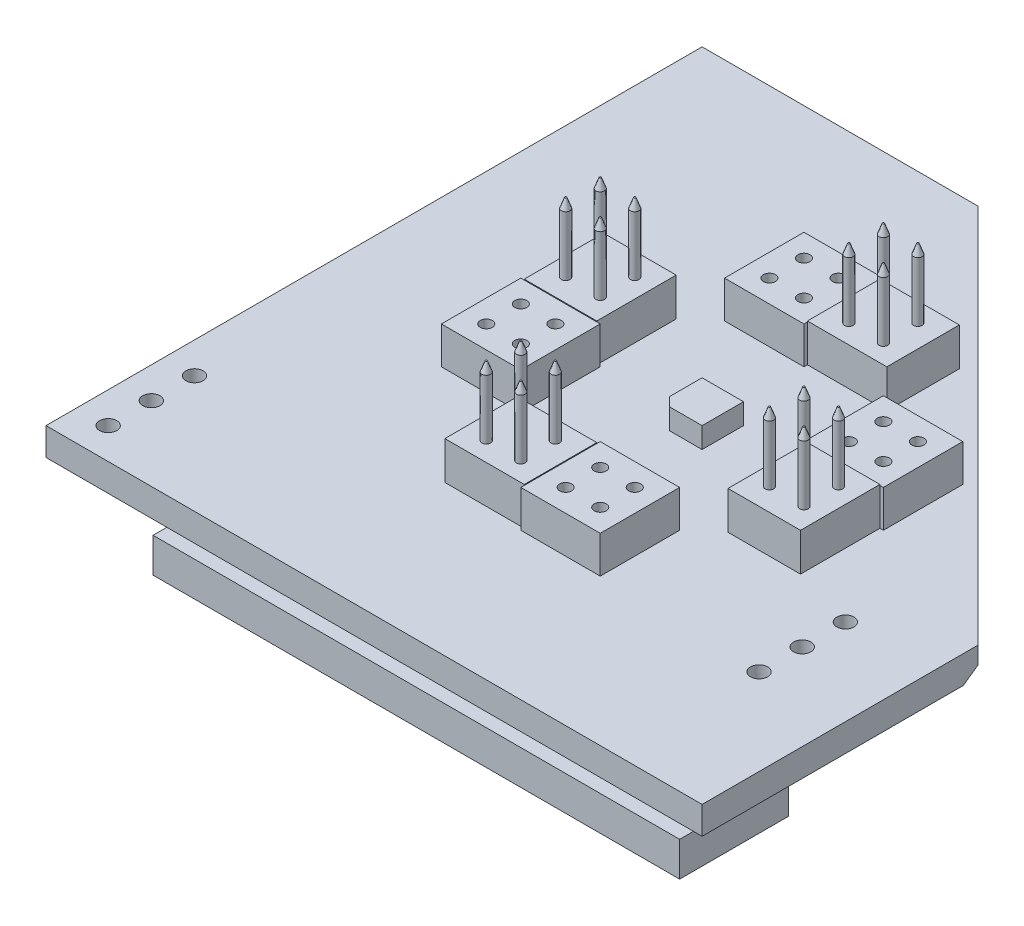
SolidWorks part; units mm, degrees
ref_plane "Front" through (0, 0, 0) normal (0, 0, 1) x (1, 0, 0)
ref_plane "Top" through (0, 0, 0) normal (0, 1, 0) x (1, 0, 0)
ref_plane "Right" through (0, 0, 0) normal (1, 0, 0) x (0, 0, -1)
sketch "Sketch1" plane through (0, 0, 0) normal (0, 1, 0) x (1, 0, 0)
  line L0 (19, -3.0194) -> (-3.0194, 19)
  line L1 (-19, 19) -> (-3.0194, 19)
  line L2 (-19, 19) -> (-19, -19)
  line L3 (-19, -19) -> (19, -19)
  line L4 (19, -3.0194) -> (19, -19)
  dimension "D1" = 19
  dimension "D2" = 19
  dimension "D3" = 19
  dimension "D4" = 19
  dimension "D5" = 45
  dimension "D6" = 11.3
extrude "Extrude1" add sketch "Sketch1" along normal blind 1.6
sketch "Sketch2" plane through (0, 1.6, 0) normal (0, 1, 0) x (-1, 0, 0)
  line L0 (-10.5, -4.6) -> (-10.5, 0)
  line L1 (4.6, -10.5) -> (0, -10.5)
  line L2 (4.6, -10.5) -> (4.6, -5.9)
  line L3 (4.6, -5.9) -> (0, -5.9)
  line L4 (0, -10.5) -> (0, -5.9)
  line L5 (-10.5, -4.6) -> (-5.9, -4.6)
  line L6 (-5.9, -4.6) -> (-5.9, 0)
  line L7 (-10.5, 0) -> (-5.9, 0)
  line L8 (-4.6, 10.5) -> (0, 10.5)
  line L9 (-4.6, 10.5) -> (-4.6, 5.9)
  line L10 (-4.6, 5.9) -> (0, 5.9)
  line L11 (0, 10.5) -> (0, 5.9)
  line L12 (10.5, 4.6) -> (10.5, 0)
  line L13 (10.5, 4.6) -> (5.9, 4.6)
  line L14 (5.9, 4.6) -> (5.9, 0)
  line L15 (10.5, 0) -> (5.9, 0)
  dimension "D1" = 4.6
  dimension "D2" = 4.6
  dimension "D3" = 5.9
  dimension "D4" = 5.9
extrude "Extrude2" add sketch "Sketch2" along normal blind 2.15
sketch "Sketch3" plane through (0, 1.6, 0) normal (0, 1, 0) x (-1, 0, 0)
  line L0 (0, -5.9) -> (0, -10.5) construction
  line L1 (-4.6, -10.3) -> (0, -10.3)
  line L2 (-4.6, -10.3) -> (-4.6, -6.1)
  line L3 (-4.6, -6.1) -> (0, -6.1)
  line L4 (0, -10.3) -> (0, -6.1)
  line L5 (-6.1, 4.6) -> (-6.1, 0)
  line L6 (-10.3, 0) -> (-6.1, 0)
  line L7 (-10.3, 4.6) -> (-6.1, 4.6)
  line L8 (-10.3, 4.6) -> (-10.3, 0)
  line L9 (4.6, 6.1) -> (0, 6.1)
  line L10 (0, 10.3) -> (0, 6.1)
  line L11 (4.6, 10.3) -> (4.6, 6.1)
  line L12 (4.6, 10.3) -> (0, 10.3)
  line L13 (6.1, -4.6) -> (6.1, 0)
  line L14 (10.3, 0) -> (6.1, 0)
  line L15 (10.3, -4.6) -> (6.1, -4.6)
  line L16 (10.3, -4.6) -> (10.3, 0)
  dimension "D1" = 4.6
  dimension "D2" = 4.2
  dimension "D3" = 6.1
  dimension "D4" = 6.1
extrude "Extrude3" add sketch "Sketch3" along normal blind 2.2
sketch "Sketch4" plane through (0, 3.75, 0) normal (0, 1, 0) x (-1, 0, 0)
  line L0 (2.3, -10.5) -> (2.3, -5.9) construction
  line L2 (4.6, -5.9) -> (0, -5.9) construction
  line L3 (4.6, -8.2) -> (0, -8.2) construction
  line L4 (0, -10.5) -> (4.6, -10.5) construction
  line L6 (4.6, -10.5) -> (4.6, -5.9) construction
  circle A0 centre (3.3, -9.2) radius 0.35
  circle A1 centre (1.3, -9.2) radius 0.35
  circle A2 centre (1.3, -7.2) radius 0.35
  circle A3 centre (3.3, -7.2) radius 0.35
  circle A4 centre (-9.2, -3.3) radius 0.35
  circle A5 centre (-9.2, -1.3) radius 0.35
  circle A6 centre (-7.2, -1.3) radius 0.35
  circle A7 centre (-7.2, -3.3) radius 0.35
  circle A8 centre (-3.3, 9.2) radius 0.35
  circle A9 centre (-1.3, 9.2) radius 0.35
  circle A10 centre (-1.3, 7.2) radius 0.35
  circle A11 centre (-3.3, 7.2) radius 0.35
  circle A12 centre (9.2, 3.3) radius 0.35
  circle A13 centre (9.2, 1.3) radius 0.35
  circle A14 centre (7.2, 1.3) radius 0.35
  circle A15 centre (7.2, 3.3) radius 0.35
  dimension "D3" = 0.7
  dimension "D1" = 1
  dimension "D2" = 1
extrude "Cut-Extrude1" cut sketch "Sketch4" against normal up to surface (2.15 mm away) up to face at (0, 1.6, 8.2)
sketch "Sketch5" plane through (0, 3.8, 0) normal (0, 1, 0) x (-1, 0, 0)
  line L0 (-2.3, -10.3) -> (-2.3, -6.1) construction
  line L1 (-4.6, -10.3) -> (0, -10.3) construction
  line L2 (0, -6.1) -> (-4.6, -6.1) construction
  line L3 (0, -8.2) -> (-4.6, -8.2) construction
  line L4 (0, -10.3) -> (0, -6.1) construction
  line L5 (-4.6, -6.1) -> (-4.6, -10.3) construction
  circle A0 centre (-1.3, -9.2) radius 0.25
  circle A1 centre (-3.3, -9.2) radius 0.25
  circle A2 centre (-3.3, -7.2) radius 0.25
  circle A3 centre (-1.3, -7.2) radius 0.25
  circle A4 centre (-7.2, 1.3) radius 0.25
  circle A5 centre (-9.2, 1.3) radius 0.25
  circle A6 centre (-9.2, 3.3) radius 0.25
  circle A7 centre (-7.2, 3.3) radius 0.25
  circle A8 centre (1.3, 7.2) radius 0.25
  circle A9 centre (1.3, 9.2) radius 0.25
  circle A10 centre (3.3, 9.2) radius 0.25
  circle A11 centre (3.3, 7.2) radius 0.25
  circle A12 centre (7.2, -1.3) radius 0.25
  circle A13 centre (9.2, -1.3) radius 0.25
  circle A14 centre (9.2, -3.3) radius 0.25
  circle A15 centre (7.2, -3.3) radius 0.25
  dimension "D3" = 0.5
  dimension "D1" = 1
  dimension "D2" = 1
extrude "Extrude4" add sketch "Sketch5" along normal blind 4
chamfer "Chamfer1" distance 0.2 angle 70 16 edges at (-1.3, 7.8, 9.45) (-3.3, 7.8, 8.95) (-3.3, 7.8, 7.45) (-1.3, 7.8, 6.95) (7.2, 7.8, 3.55) (9.2, 7.8, 3.05) (9.2, 7.8, 1.55) (7.2, 7.8, 1.05) (1.3, 7.8, -7.45) (3.3, 7.8, -6.95) (3.3, 7.8, -9.45) (1.3, 7.8, -8.95) (-9.2, 7.8, -1.05) (-7.2, 7.8, -3.05) (-9.2, 7.8, -3.55) (-7.2, 7.8, -1.55)
sketch "Sketch6" plane through (0, 0, 0) normal (0, -1, 0) x (1, 0, 0)
  line L1 (-19, 19) -> (19, 19) construction
  line L2 (19, 19) -> (19, 3.0194) construction
  line L9 (18.5, 13.5) -> (18.5, 19.8)
  line L10 (18.5, 19.8) -> (-12, 19.8)
  line L11 (-12, 19.8) -> (-12, 13.5)
  line L12 (-12, 13.5) -> (18.5, 13.5)
  dimension "D1" = 0.8
  dimension "D2" = 0.5
  dimension "D3" = 6.3
  dimension "D4" = 30.5
extrude "Extrude5" add sketch "Sketch6" along normal blind 2
sketch "Sketch7" plane through (0, 0, 0) normal (0, -1, 0) x (1, 0, 0)
  line L0 (-19, 19) -> (-12, 19) construction
  line L1 (-8.75, 3.25) -> (-1.75, 3.25)
  line L2 (-8.75, 3.25) -> (-8.75, -3.75)
  line L3 (-8.75, -3.75) -> (-1.75, -3.75)
  line L4 (-1.75, 3.25) -> (-1.75, -3.75)
  line L5 (-19, -19) -> (-19, 19) construction
  dimension "D1" = 7
  dimension "D2" = 7
  dimension "D3" = 15.75
  dimension "D4" = 10.25
extrude "Extrude6" [suppressed] add sketch "Sketch7" along normal blind 1
chamfer "Chamfer2" distance 0.6 angle 45 1 edges at (7.9903, 0, -7.9903)
sketch "Sketch8" plane through (0, 1.6, 0) normal (0, 1, 0) x (-1, 0, 0)
  line L0 (1.2, 0.7) -> (0.7, 1.2)
  line L1 (1.2, -1.2) -> (-1.2, -1.2)
  line L2 (1.2, -1.2) -> (1.2, 0.7)
  line L3 (0.7, 1.2) -> (-1.2, 1.2)
  line L4 (-1.2, -1.2) -> (-1.2, 1.2)
  dimension "D1" = 1.2
  dimension "D2" = 1.2
  dimension "D3" = 1.2
  dimension "D4" = 1.2
  dimension "D5" = 0.5
  dimension "D6" = 0.5
extrude "Extrude7" add sketch "Sketch8" along normal blind 1.2
sketch "Sketch9" plane through (0, 0, 0) normal (0, -1, 0) x (1, 0, 0)
  line L0 (19, 19) -> (19, 3.8679) construction
  line L1 (9.5, 1.7) -> (7.5, 1.7)
  line L2 (9.5, 1.7) -> (9.5, -0.3)
  line L3 (9.5, -0.3) -> (7.5, -0.3)
  line L4 (7.5, 1.7) -> (7.5, -0.3)
  line L5 (18.5, 19) -> (19, 19) construction
  line L6 (-19, 19) -> (-12, 19) construction
  line L7 (-0.35, 6.15) -> (-2.35, 6.15)
  line L8 (-0.35, 6.15) -> (-0.35, 4.15)
  line L9 (-0.35, 4.15) -> (-2.35, 4.15)
  line L10 (-2.35, 6.15) -> (-2.35, 4.15)
  dimension "D1" = 9.5
  dimension "D2" = 17.3
  dimension "D3" = 2
  dimension "D4" = 2
  dimension "D5" = 19.35
  dimension "D6" = 12.85
  dimension "D7" = 2
  dimension "D8" = 2
extrude "Extrude8" [suppressed] add sketch "Sketch9" along normal blind 0.9
sketch "Sketch10" plane through (0, 0, 0) normal (0, -1, 0) x (1, 0, 0)
  line L0 (19, 19) -> (19, 3.8679) construction
  line L1 (1.35, 2.8) -> (0.6, 2.8)
  line L2 (1.55, 2.6) -> (1.55, -0.2)
  line L3 (1.35, -0.4) -> (0.6, -0.4)
  line L4 (0.4, 2.6) -> (0.4, -0.2)
  line L5 (-19, 19) -> (-12, 19) construction
  arc A0 (0.4, -0.2) -> (0.6, -0.4) centre (0.6, -0.2) ccw
  arc A1 (0.6, 2.8) -> (0.4, 2.6) centre (0.6, 2.6) ccw
  arc A2 (1.55, 2.6) -> (1.35, 2.8) centre (1.35, 2.6) ccw
  arc A3 (1.35, -0.4) -> (1.55, -0.2) centre (1.35, -0.2) ccw
  point P10 (0.4, -0.4)
  point P15 (1.55, 2.8)
  point P18 (1.55, -0.4)
  dimension "D5" = 0.2
  dimension "D1" = 17.45
  dimension "D2" = 16.2
  dimension "D3" = 1.15
  dimension "D4" = 3.2
extrude "Extrude9" [suppressed] add sketch "Sketch10" along normal blind 1
sketch "Sketch11" plane through (0, 0, 0) normal (0, -1, 0) x (1, 0, 0)
  line L0 (19, 19) -> (19, 3.8679) construction
  line L1 (9.35, 6.9) -> (7.75, 6.9)
  line L2 (9.35, 6.9) -> (9.35, 6.1)
  line L3 (9.35, 6.1) -> (7.75, 6.1)
  line L4 (7.75, 6.9) -> (7.75, 6.1)
  line L5 (-19, 19) -> (-12, 19) construction
  line L6 (-19, -19) -> (-19, 19) construction
  line L7 (-10.15, -6.9) -> (-10.95, -6.9)
  line L8 (-10.15, -6.9) -> (-10.15, -5.3)
  line L9 (-10.15, -5.3) -> (-10.95, -5.3)
  line L10 (-10.95, -6.9) -> (-10.95, -5.3)
  line L11 (-3.8679, -19) -> (-19, -19) construction
  line L12 (-19, -19) -> (-19, 19) construction
  line L13 (-2.9, -14.85) -> (-3.7, -14.85)
  line L14 (-2.9, -14.85) -> (-2.9, -13.25)
  line L15 (-2.9, -13.25) -> (-3.7, -13.25)
  line L16 (-3.7, -14.85) -> (-3.7, -13.25)
  line L18 (-0.3, -12.1) -> (-1.1, -12.1)
  line L19 (-0.3, -12.1) -> (-0.3, -10.5)
  line L20 (-0.3, -10.5) -> (-1.1, -10.5)
  line L21 (-1.1, -12.1) -> (-1.1, -10.5)
  point P20 (-19, 0)
  point P27 (-19, 0)
  dimension "D1" = 9.65
  dimension "D2" = 12.1
  dimension "D3" = 1.6
  dimension "D4" = 0.8
  dimension "D5" = 8.05
  dimension "D6" = 12.1
  dimension "D7" = 1.6
  dimension "D8" = 0.8
  dimension "D9" = 15.3
  dimension "D10" = 4.15
  dimension "D11" = 1.6
  dimension "D12" = 0.8
  dimension "D13" = 17.9
  dimension "D14" = 6.9
  dimension "D15" = 1.6
  dimension "D16" = 0.8
extrude "Extrude10" [suppressed] add sketch "Sketch11" along normal blind 0.5
sketch "Sketch12" plane through (0, 0, 0) normal (0, -1, 0) x (1, 0, 0)
  line L0 (-19, -19) -> (-19, 19) construction
  line L1 (-11.3, -16.3) -> (-9.6, -16.3)
  line L2 (-11.3, -16.3) -> (-11.3, -12.6)
  line L3 (-11.3, -12.6) -> (-10.6, -12.6)
  line L4 (-4.6, -16.3) -> (-4.6, -12.6)
  line L5 (-3.8679, -19) -> (-19, -19) construction
  line L6 (-6.4, -16.3) -> (-4.6, -16.3)
  line L7 (-9.7, -12.6) -> (-8.45, -12.6)
  line L8 (-6.4, -16.3) -> (-6.4, -18.2)
  line L9 (-6.4, -18.2) -> (-9.6, -18.2)
  line L10 (-9.6, -16.3) -> (-9.6, -18.2)
  line L11 (-5.3, -12.6) -> (-4.6, -12.6)
  line L12 (-5.3, -12.6) -> (-5.3, -10.7)
  line L13 (-5.3, -10.7) -> (-6.2, -10.7)
  line L14 (-6.2, -12.6) -> (-6.2, -10.7)
  line L16 (-7.55, -12.6) -> (-7.55, -10.7)
  line L17 (-7.55, -10.7) -> (-8.45, -10.7)
  line L18 (-8.45, -12.6) -> (-8.45, -10.7)
  line L19 (-7.55, -12.6) -> (-6.2, -12.6)
  line L20 (-9.7, -12.6) -> (-9.7, -10.7)
  line L21 (-9.7, -10.7) -> (-10.6, -10.7)
  line L22 (-10.6, -12.6) -> (-10.6, -10.7)
  dimension "D1" = 7.7
  dimension "D2" = 2.7
  dimension "D3" = 6.7
  dimension "D4" = 3.7
  dimension "D5" = 1.9
  dimension "D6" = 3.2
  dimension "D7" = 1.7
  dimension "D8" = 0.9
  dimension "D9" = 1.9
  dimension "D10" = 0.9
  dimension "D11" = 1.9
  dimension "D12" = 0.9
  dimension "D13" = 1.9
  dimension "D14" = 2.85
  dimension "D15" = 0.7
  dimension "D16" = 0.7
extrude "Extrude11" [suppressed] add sketch "Sketch12" along normal blind 0.3
sketch "Sketch13" [suppressed] plane through (0, -0.3, 0) normal (0, -1, 0) x (1, 0, 0)
  line L1 (-4.61, -16.29) -> (-11.29, -16.29)
  line L2 (-4.61, -16.29) -> (-4.61, -12.61)
  line L3 (-4.61, -12.61) -> (-11.29, -12.61)
  line L4 (-11.29, -16.29) -> (-11.29, -12.61)
  line L5 (-6.4, -16.3) -> (-4.6, -16.3) construction
  line L6 (-4.6, -16.3) -> (-4.6, -12.6) construction
  line L7 (-11.3, -12.6) -> (-11.3, -16.3) construction
  line L8 (-10.6, -12.6) -> (-11.3, -12.6) construction
  dimension "D1" = 0.01
  dimension "D2" = 0.01
  dimension "D3" = 0.01
  dimension "D4" = 0.01
extrude "Extrude12" [suppressed] add sketch "Sketch13" along normal blind 1.5
sketch "Sketch14" plane through (0, 0, 0) normal (0, -1, 0) x (1, 0, 0)
  line L0 (-19, -19) -> (-19, 19) construction
  line L1 (-19, 19) -> (-12, 19) construction
  line L2 (-19, -19) -> (-19, 19) construction
  line L3 (18.5, 19) -> (19, 19) construction
  line L4 (19, 19) -> (19, 3.8679) construction
  circle A0 centre (-17.2, 17.2) radius 0.5
  circle A1 centre (-17.2, 14.7) radius 0.5
  circle A2 centre (-17.2, 12.2) radius 0.5
  circle A3 centre (14, 8.2) radius 0.5
  circle A4 centre (14, 5.7) radius 0.5
  circle A6 centre (14, 10.7) radius 0.5
  dimension "D1" = 1
  dimension "D5" = 5
  dimension "D7" = 5
  dimension "D8" = 1
  dimension "D2" = 1.8
  dimension "D3" = 1.8
  dimension "D4" = 1.8
  dimension "D6" = 8.3
  dimension "D9" = 5
  dimension "D10" = 5
extrude "Cut-Extrude2" cut sketch "Sketch14" against normal through all
sketch "Sketch15" plane through (0, 0, 0) normal (0, -1, 0) x (1, 0, 0)
  line L1 (19, 19) -> (19, 3.8679) construction
  line L2 (-19, -19) -> (-19, 19) construction
  circle A0 centre (14, 10.7) radius 0.5 construction
  circle A1 centre (14, 10.7) radius 0.5
  circle A2 centre (14, 10.7) radius 0.95
  circle A3 centre (14, 8.2) radius 0.5
  circle A4 centre (14, 8.2) radius 0.95
  circle A5 centre (14, 5.7) radius 0.5
  circle A6 centre (14, 5.7) radius 0.95
  circle A8 centre (-17.2, 17.2) radius 0.5 construction
  circle A10 centre (-17.2, 17.2) radius 0.5
  circle A12 centre (-17.2, 17.2) radius 0.95
  circle A14 centre (-17.2, 14.7) radius 0.5
  circle A16 centre (-17.2, 14.7) radius 0.95
  circle A18 centre (-17.2, 12.2) radius 0.5
  circle A20 centre (-17.2, 12.2) radius 0.95
  dimension "D4" = 0.45
  dimension "D1" = 0.45
  dimension "D2" = 5
  dimension "D3" = 5
  dimension "D5" = 1.8
  dimension "D6" = 5
extrude "Extrude13" add sketch "Sketch15" along normal blind 0.05 and the other way blind 1.05
sketch "Sketch16" plane through (0, 0, 0) normal (0, -1, 0) x (1, 0, 0)
  line L0 (-19, -19) -> (-19, 19) construction
  line L1 (-7.2, -8.2) -> (-10.6, -8.2)
  line L2 (-7.2, -8.2) -> (-7.2, -9.9)
  line L3 (-7.2, -9.9) -> (-10.6, -9.9)
  line L4 (-10.6, -8.2) -> (-10.6, -9.9)
  line L5 (-3.8679, -19) -> (-19, -19) construction
  dimension "D1" = 8.4
  dimension "D2" = 9.1
  dimension "D3" = 1.7
  dimension "D4" = 3.4
extrude "Extrude14" [suppressed] add sketch "Sketch16" along normal blind 1.6
sketch "Sketch17" plane through (0, 0, 0) normal (0, -1, 0) x (1, 0, 0)
  line L0 (-19, -19) -> (-19, 19) construction
  line L1 (-8.05, -5) -> (-9.25, -5)
  line L2 (-8.05, -5) -> (-8.05, -7.3)
  line L3 (-8.05, -7.3) -> (-9.25, -7.3)
  line L4 (-9.25, -5) -> (-9.25, -7.3)
  line L5 (-3.8679, -19) -> (-19, -19) construction
  point P4 (-19, 0)
  dimension "D1" = 9.75
  dimension "D2" = 11.7
  dimension "D3" = 1.2
  dimension "D4" = 2.3
extrude "Extrude15" [suppressed] add sketch "Sketch17" along normal blind 1.3
sketch "Sketch18" plane through (0, 0, 0) normal (0, -1, 0) x (1, 0, 0)
  line L0 (-19, -19) -> (-19, 19) construction
  line L1 (-3.65, -12.05) -> (-1.65, -12.05)
  line L2 (-3.65, -12.05) -> (-3.65, -11.05)
  line L3 (-3.65, -11.05) -> (-1.65, -11.05)
  line L4 (-1.65, -12.05) -> (-1.65, -11.05)
  line L5 (-3.8679, -19) -> (-19, -19) construction
  point P4 (-19, 0)
  dimension "D1" = 15.35
  dimension "D2" = 6.95
  dimension "D3" = 2
  dimension "D4" = 1
extrude "Extrude16" [suppressed] add sketch "Sketch18" along normal blind 0.5
sketch "Sketch19" plane through (0, 0, 0) normal (0, -1, 0) x (1, 0, 0)
  line L0 (-19, -19) -> (-19, 19) construction
  line L1 (-0.8, -8.45) -> (0.45, -8.45)
  line L2 (-0.8, -8.45) -> (-0.8, -7)
  line L3 (-0.8, -7) -> (-0.5, -7)
  line L4 (2.25, -8.45) -> (2.25, -7)
  line L5 (-3.8679, -19) -> (-19, -19) construction
  line L6 (1.95, -7) -> (2.25, -7)
  line L8 (0.95, -8.45) -> (0.95, -9.05)
  line L9 (0.95, -9.05) -> (0.45, -9.05)
  line L10 (0.45, -8.45) -> (0.45, -9.05)
  line L11 (0, -7) -> (1.45, -7)
  line L12 (1.95, -7) -> (1.95, -6.4)
  line L13 (1.95, -6.4) -> (1.45, -6.4)
  line L14 (1.45, -7) -> (1.45, -6.4)
  line L15 (0.95, -8.45) -> (2.25, -8.45)
  line L16 (0, -7) -> (0, -6.4)
  line L17 (0, -6.4) -> (-0.5, -6.4)
  line L18 (-0.5, -7) -> (-0.5, -6.4)
  dimension "D1" = 18.2
  dimension "D2" = 10.55
  dimension "D3" = 1.45
  dimension "D4" = 3.05
  dimension "D5" = 0.5
  dimension "D6" = 0.6
  dimension "D7" = 0.5
  dimension "D8" = 0.5
  dimension "D9" = 0.6
  dimension "D10" = 0.6
  dimension "D11" = 1.25
  dimension "D12" = 0.3
  dimension "D13" = 0.3
extrude "Extrude17" [suppressed] add sketch "Sketch19" along normal blind 0.3
sketch "Sketch20" [suppressed] plane through (0, -0.3, 0) normal (0, -1, 0) x (1, 0, 0)
  line L0 (-0.8, -7) -> (-0.8, -8.45) construction
  line L1 (-0.79, -7.01) -> (2.24, -7.01)
  line L2 (-0.79, -7.01) -> (-0.79, -8.44)
  line L3 (-0.79, -8.44) -> (2.24, -8.44)
  line L4 (2.24, -7.01) -> (2.24, -8.44)
  line L5 (-0.5, -7) -> (-0.8, -7) construction
  line L6 (-0.8, -8.45) -> (0.45, -8.45) construction
  line L7 (2.25, -8.45) -> (2.25, -7) construction
  dimension "D1" = 0.01
  dimension "D2" = 0.01
  dimension "D3" = 0.01
  dimension "D4" = 0.01
extrude "Extrude18" [suppressed] add sketch "Sketch20" along normal blind 0.8
sketch "Sketch21" plane through (0, 0, 0) normal (0, -1, 0) x (1, 0, 0)
  line L0 (-19, 19) -> (-12, 19) construction
  line L1 (4.1, 5.45) -> (0.85, 5.45)
  line L2 (4.1, 5.45) -> (4.1, 2.2)
  line L3 (4.1, 2.2) -> (0.85, 2.2)
  line L4 (0.85, 5.45) -> (0.85, 2.2)
  line L5 (19, 19) -> (19, 3.8679) construction
  dimension "D1" = 13.55
  dimension "D2" = 14.9
  dimension "D3" = 3.25
  dimension "D4" = 3.25
extrude "Extrude19" add sketch "Sketch21" along normal blind 1.1
sketch "Sketch22" plane through (0, 0, 0) normal (0, -1, 0) x (1, 0, 0)
  line L0 (19, 19) -> (19, 3.8679) construction
  line L1 (12.25, 10.9) -> (11.45, 10.9)
  line L2 (12.25, 10.9) -> (12.25, 9.3)
  line L3 (12.25, 9.3) -> (11.45, 9.3)
  line L4 (11.45, 10.9) -> (11.45, 9.3)
  line L5 (12.25, 7.4) -> (11.45, 7.4)
  line L6 (12.25, 7.4) -> (12.25, 5.8)
  line L7 (12.25, 5.8) -> (11.45, 5.8)
  line L8 (11.45, 7.4) -> (11.45, 5.8)
  line L9 (5.45, -0.65) -> (4.65, -0.65)
  line L10 (5.45, -0.65) -> (5.45, -2.25)
  line L11 (5.45, -2.25) -> (4.65, -2.25)
  line L12 (4.65, -0.65) -> (4.65, -2.25)
  line L13 (3.95, -0.65) -> (3.15, -0.65)
  line L14 (3.95, -0.65) -> (3.95, -2.25)
  line L15 (3.95, -2.25) -> (3.15, -2.25)
  line L16 (3.15, -0.65) -> (3.15, -2.25)
  line L17 (0.65, -0.15) -> (-0.15, -0.15)
  line L18 (0.65, -0.15) -> (0.65, -1.75)
  line L19 (0.65, -1.75) -> (-0.15, -1.75)
  line L20 (-0.15, -0.15) -> (-0.15, -1.75)
  line L21 (-19, 19) -> (-12, 19) construction
  line L22 (18.5, 19) -> (19, 19) construction
  line L23 (8, 3.5) -> (6, 3.5)
  line L24 (8, 3.5) -> (8, 2.2)
  line L25 (8, 2.2) -> (6, 2.2)
  line L26 (6, 3.5) -> (6, 2.2)
  line L27 (-19, -19) -> (-19, 19) construction
  line L28 (-5.15, 3.05) -> (-5.95, 3.05)
  line L29 (-5.15, 3.05) -> (-5.15, 1.45)
  line L30 (-5.15, 1.45) -> (-5.95, 1.45)
  line L31 (-5.95, 3.05) -> (-5.95, 1.45)
  line L32 (-3.8679, -19) -> (-19, -19) construction
  line L33 (-13.85, -4.6) -> (-14.65, -4.6)
  line L34 (-13.85, -4.6) -> (-13.85, -6.2)
  line L35 (-13.85, -6.2) -> (-14.65, -6.2)
  line L36 (-14.65, -4.6) -> (-14.65, -6.2)
  line L38 (-14.3, -1.7) -> (-15.9, -1.7)
  line L39 (-14.3, -1.7) -> (-14.3, -2.5)
  line L40 (-14.3, -2.5) -> (-15.9, -2.5)
  line L41 (-15.9, -1.7) -> (-15.9, -2.5)
  dimension "D1" = 8.1
  dimension "D2" = 6.75
  dimension "D3" = 6.75
  dimension "D4" = 3.5
  dimension "D5" = 1.6
  dimension "D6" = 1.6
  dimension "D7" = 0.8
  dimension "D8" = 0.8
  dimension "D9" = 19.65
  dimension "D10" = 13.55
  dimension "D11" = 1.5
  dimension "D12" = 0.8
  dimension "D13" = 0.8
  dimension "D14" = 1.6
  dimension "D15" = 19.15
  dimension "D16" = 18.35
  dimension "D17" = 1.6
  dimension "D18" = 0.8
  dimension "D19" = 15.5
  dimension "D20" = 11
  dimension "D21" = 1.3
  dimension "D22" = 2
  dimension "D23" = 15.95
  dimension "D24" = 13.05
  dimension "D25" = 0.8
  dimension "D26" = 1.6
  dimension "D27" = 1.6
  dimension "D28" = 0.8
  dimension "D29" = 12.8
  dimension "D30" = 4.35
  dimension "D31" = 16.5
  dimension "D32" = 3.1
  dimension "D33" = 0.8
  dimension "D34" = 1.6
extrude "Extrude20" add sketch "Sketch22" along normal blind 0.5
sketch "Sketch23" plane through (0, 0, 0) normal (0, -1, 0) x (1, 0, 0)
  line L0 (-19, 19) -> (-12, 19) construction
  line L1 (-15.35, 11.65) -> (-7.35, 11.65)
  line L2 (-16.55, 10.45) -> (-16.55, 2.45)
  line L3 (-15.35, 1.25) -> (-7.35, 1.25)
  line L4 (-6.15, 10.45) -> (-6.15, 2.45)
  line L5 (-19, -19) -> (-19, 19) construction
  line L6 (-6.15, 2.45) -> (-7.35, 1.25)
  line L7 (-16.55, 2.45) -> (-15.35, 1.25)
  line L8 (-7.35, 11.65) -> (-6.15, 10.45)
  line L9 (-15.35, 11.65) -> (-16.55, 10.45)
  point P0 (-16.55, 11.65)
  point P1 (-6.15, 1.25)
  point P2 (-16.55, 1.25)
  point P3 (-6.15, 11.65)
  dimension "D1" = 10.4
  dimension "D2" = 10.4
  dimension "D3" = 17.75
  dimension "D4" = 12.85
  dimension "D7" = 1.2
  dimension "D8" = 1.2
  dimension "D9" = 1.2
  dimension "D10" = 1.2
extrude "Extrude21" add sketch "Sketch23" along normal blind 5
sketch "Sketch24" plane through (0, 0, 0) normal (0, -1, 0) x (1, 0, 0)
  line L0 (-3.8679, -19) -> (-19, -19) construction
  line L1 (-9.8, -7.3) -> (-17.1, -7.3)
  line L2 (-9.8, -7.3) -> (-9.8, -11.55)
  line L3 (-9.8, -11.55) -> (-17.1, -11.55)
  line L4 (-17.1, -7.3) -> (-17.1, -11.55)
  line L5 (1.45, -7.15) -> (-5.85, -7.15)
  line L6 (1.45, -7.15) -> (1.45, -11.4)
  line L7 (1.45, -11.4) -> (-5.85, -11.4)
  line L8 (-5.85, -7.15) -> (-5.85, -11.4)
  line L9 (-19, -19) -> (-19, 19) construction
  dimension "D1" = 7.45
  dimension "D2" = 1.9
  dimension "D3" = 4.25
  dimension "D4" = 7.3
  dimension "D5" = 4.25
  dimension "D6" = 7.3
  dimension "D7" = 7.6
  dimension "D8" = 13.15
extrude "Extrude22" add sketch "Sketch24" along normal blind 2.8
sketch "Sketch25" plane through (0, 0, 0) normal (0, -1, 0) x (1, 0, 0)
  line L0 (-3.8679, -19) -> (-19, -19) construction
  line L1 (-6.95, 0.25) -> (-11.65, 0.25)
  line L2 (-6.95, 0.25) -> (-6.95, -5.75)
  line L3 (-6.95, -5.75) -> (-11.65, -5.75)
  line L4 (-11.65, 0.25) -> (-11.65, -5.75)
  line L5 (-19, -19) -> (-19, 19) construction
  dimension "D1" = 13.25
  dimension "D2" = 7.35
  dimension "D3" = 6
  dimension "D4" = 4.7
extrude "Extrude23" add sketch "Sketch25" along normal blind 1.5
sketch "Sketch26" plane through (0, 0, 0) normal (0, -1, 0) x (1, 0, 0)
  line L0 (-3.8679, -19) -> (-19, -19) construction
  line L1 (-2.35, -0.15) -> (-4.55, -0.15)
  line L2 (-2.35, -0.15) -> (-2.35, -4.35)
  line L3 (-2.35, -4.35) -> (-4.55, -4.35)
  line L4 (-4.55, -0.15) -> (-4.55, -4.35)
  line L5 (-19, -19) -> (-19, 19) construction
  dimension "D1" = 14.65
  dimension "D2" = 14.45
  dimension "D3" = 2.2
  dimension "D4" = 4.2
extrude "Extrude24" add sketch "Sketch26" along normal blind 2.3
